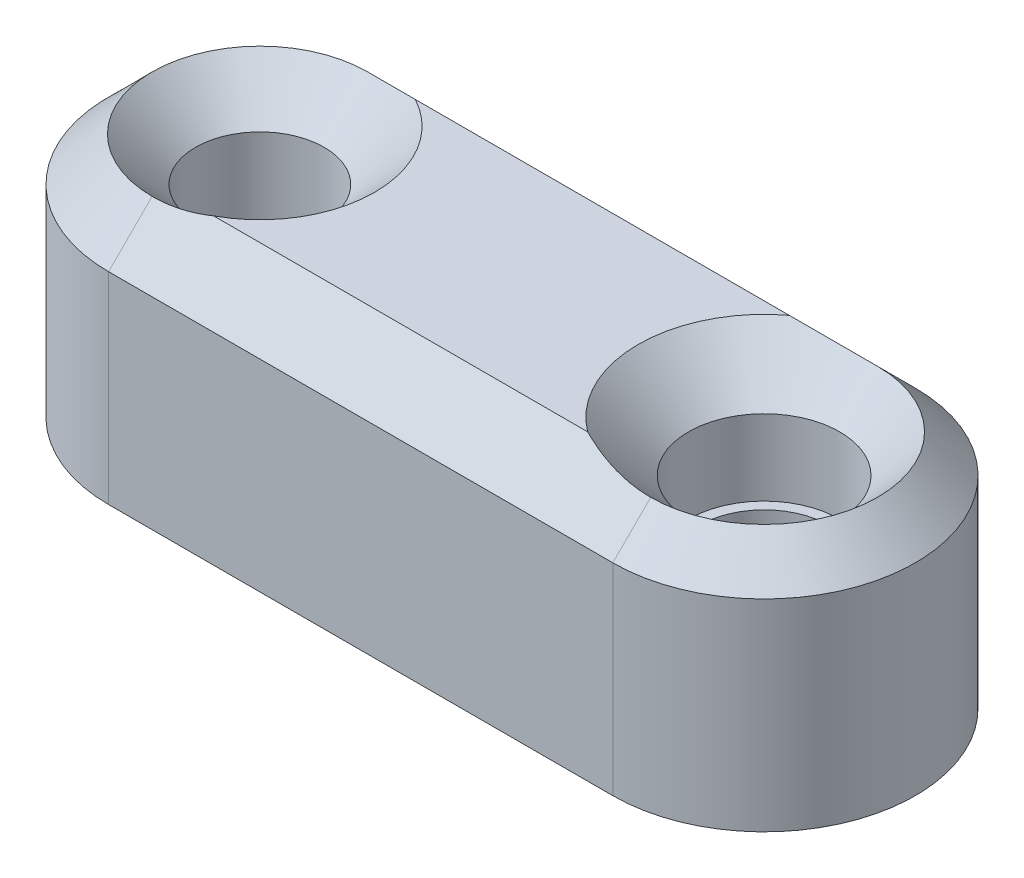
SolidWorks part; units mm, degrees
ref_plane "前视基准面" through (0, 0, 0) normal (0, 0, 1) x (1, 0, 0)
ref_plane "上视基准面" through (0, 0, 0) normal (0, 1, 0) x (1, 0, 0)
ref_plane "右视基准面" through (0, 0, 0) normal (1, 0, 0) x (0, 0, -1)
other "Configuration Table"
sketch "草图1" plane through (0, 0, 0) normal (0, 1, 0) x (1, 0, 0)
  line L0 (0, 0) -> (20, 0) construction
  line L1 (0, 6) -> (20, 6)
  line L2 (0, -6) -> (20, -6)
  arc A0 (0, 6) -> (0, -6) centre (0, 0) ccw
  arc A1 (20, -6) -> (20, 6) centre (20, 0) ccw
  point P3 (10, 0)
  dimension "D1" = 20
  dimension "D2" = 12
extrude "凸台-拉伸1" add sketch "草图1" along normal blind 10
sketch "草图2" plane through (0, 0, 0) normal (0, 0, 1) x (1, 0, 0)
  line L0 (-2.55, 10) -> (-2.55, 5)
  line L1 (0, 10) -> (-6, 10) construction
  line L2 (-2.55, 5) -> (-1.6, 5)
  line L3 (-1.6, 5) -> (-1.6, 2)
  line L4 (-1.6, 2) -> (-2.55, 2)
  line L5 (-2.55, 2) -> (-2.55, 0)
  line L7 (-2.55, 0) -> (0, 0)
  line L8 (0, 0) -> (0, 10) construction
  line L9 (0, 10) -> (-2.55, 10)
  line L10 (0, 10) -> (0, 0)
  dimension "D1" = 5.1
  dimension "D2" = 3.2
  dimension "D3" = 5
  dimension "D4" = 3
revolve "切除-旋转1" cut sketch "草图2" angle 360 about L8
sketch "草图3" plane through (0, 0, 0) normal (0, 0, 1) x (1, 0, 0)
  line L0 (20, 10) -> (20, 0) construction
  line L1 (20, 0) -> (17.425, 0)
  line L2 (0, 0) -> (20, 0) construction
  line L3 (17.425, 0) -> (17.425, 5)
  line L4 (17.425, 5) -> (17, 5)
  line L5 (17, 5) -> (17, 10)
  line L6 (0, 10) -> (20, 10) construction
  line L7 (17, 10) -> (20, 10)
  line L8 (20, 10) -> (20, 0)
  dimension "D1" = 5.15
  dimension "D2" = 6
  dimension "D3" = 5
revolve "切除-旋转2" cut sketch "草图3" angle 360 about L0
chamfer "倒角1" distance 2 angle 45 6 edges at (10, 10, -6) (26, 10, 0) (10, 10, 6) (-6, 10, 0) (0, 10, -2.55) (20, 10, 3)
sketch "草图4" plane through (0, 0, 0) normal (0, -1, 0) x (1, 0, 0)
  line L0 (20, -6) -> (0, -6) construction
  line L1 (-2.1073, -3.65) -> (2.1073, -3.65)
  line L2 (2.1073, -3.65) -> (4.2147, 0)
  line L3 (4.2147, 0) -> (2.1073, 3.65)
  line L4 (2.1073, 3.65) -> (-2.1073, 3.65)
  line L5 (-2.1073, 3.65) -> (-4.2147, 0)
  line L6 (-4.2147, 0) -> (-2.1073, -3.65)
  circle A0 centre (0, 0) radius 3.65 construction
  dimension "D1" = 7.3
extrude "切除-拉伸1" cut sketch "草图4" against normal blind 5
